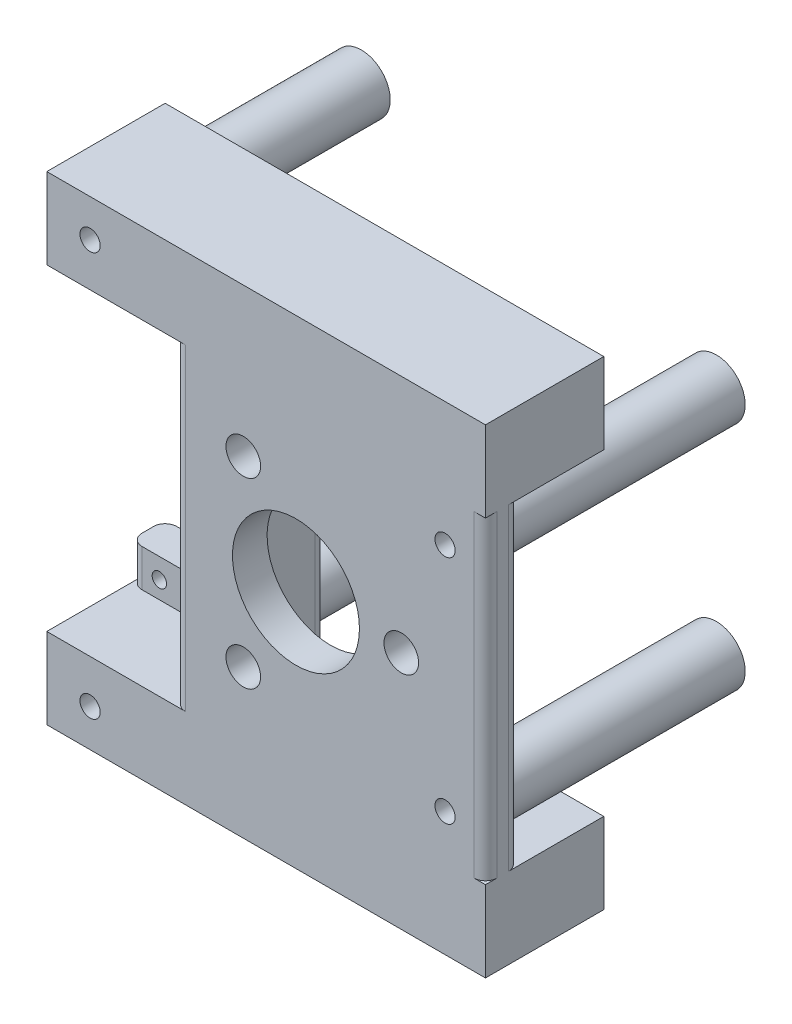
SolidWorks part; units mm, degrees
ref_plane "Front Plane" through (0, 0, 0) normal (0, 0, 1) x (1, 0, 0)
ref_plane "Top Plane" through (0, 0, 0) normal (0, 1, 0) x (1, 0, 0)
ref_plane "Right Plane" through (0, 0, 0) normal (1, 0, 0) x (0, 0, -1)
sketch "Sketch1" plane through (0, 0, 0) normal (0, 0, 1) x (1, 0, 0)
  line L0 (0, 52) -> (28, 52) construction
  line L1 (0, 0) -> (28, 0)
  line L2 (0, 0) -> (0, 55)
  line L3 (0, 55) -> (28, 55)
  line L4 (28, 0) -> (28, 55)
  line L5 (0, 3) -> (28, 3) construction
  circle A0 centre (5, 52) radius 1.25
  circle A1 centre (15, 52) radius 1.25
  circle A2 centre (5, 3) radius 1.25
  circle A3 centre (15, 3) radius 1.25
  dimension "D3" = 2.5
  dimension "D1" = 28
  dimension "D2" = 55
  dimension "D4" = 5
  dimension "D5" = 5
  dimension "D6" = 10
  dimension "D7" = 10
  dimension "D8" = 3
  dimension "D9" = 3
extrude "Boss-Extrude1" add sketch "Sketch1" along normal blind 6
sketch "Sketch2" plane through (0, 0, 6) normal (0, 0, 1) x (1, 0, 0)
  line L0 (0, 0) -> (28, 0) construction
  line L1 (28, 55) -> (22, 55)
  line L2 (28, 55) -> (28, 0)
  line L3 (28, 0) -> (22, 0)
  line L4 (22, 55) -> (22, 0)
  dimension "D1" = 6
extrude "Boss-Extrude2" add sketch "Sketch2" along normal blind 14.5
sketch "Sketch3" plane through (28, 0, 0) normal (1, 0, 0) x (0, 0, -1)
  line L0 (-20.5, 0) -> (0, 0) construction
  line L1 (-20.5, 55) -> (-14.5, 55)
  line L2 (-20.5, 55) -> (-20.5, 0)
  line L3 (-20.5, 0) -> (-14.5, 0)
  line L4 (-14.5, 55) -> (-14.5, 0)
  dimension "D1" = 6
extrude "Boss-Extrude3" add sketch "Sketch3" along normal blind 48
sketch "Sketch4" plane through (0, 0, 20.5) normal (0, 0, 1) x (1, 0, 0)
  line L0 (34.0412, 55) -> (34.0412, 43.305) construction
  line L1 (76, 55) -> (22, 55) construction
  line L2 (22, 55) -> (22, 0) construction
  line L3 (22, 0) -> (76, 0) construction
  line L5 (43.1662, 27.5) -> (32.5412, 45.903) construction
  line L6 (34.0412, 11.695) -> (43.1662, 27.5) construction
  line L7 (43.1662, 27.5) -> (61.4162, 27.5) construction
  line L8 (22, 18) -> (0, 18) construction
  line L9 (0, 55) -> (0, 0) construction
  line L10 (10, 18) -> (43.1662, 27.5) construction
  line L11 (34.0412, 11.695) -> (34.0412, 0) construction
  line L12 (0, 0) -> (22, 0) construction
  circle A0 centre (61.4162, 27.5) radius 3
  circle A1 centre (34.0412, 11.695) radius 3
  circle A2 centre (43.1662, 27.5) radius 21.25 construction
  circle A3 centre (34.0412, 43.305) radius 3
  circle A4 centre (43.1662, 27.5) radius 11
  point P18 (10, 18)
  dimension "D2" = 42.5
  dimension "D3" = 6
  dimension "D4" = 120
  dimension "D8" = 22
  dimension "D1" = 120
  dimension "D5" = 10
  dimension "D6" = 34.5
  dimension "D7" = 18
extrude "Cut-Extrude1" cut sketch "Sketch4" against normal blind 48
fillet "Fillet4" radius 2 7 edges at (22, 27.5, 20.5) (0, 27.5, 6) (0, 27.5, 0) (76, 27.5, 14.5) (28, 27.5, 0) (76, 27.5, 20.5)
sketch "Sketch5" plane through (0, 0, 6) normal (0, 0, 1) x (1, 0, 0)
  line L0 (22, 55) -> (2, 55) construction
  line L1 (0, 48.5) -> (21, 48.5)
  line L2 (0, 48.5) -> (0, 6.5)
  line L3 (0, 6.5) -> (21, 6.5)
  line L4 (21, 48.5) -> (21, 6.5)
  line L5 (2, 0) -> (22, 0) construction
  line L8 (0, 0) -> (0, 55) construction
  dimension "D1" = 6.5
  dimension "D2" = 6.5
  dimension "D3" = 21
extrude "Cut-Extrude2" cut sketch "Sketch5" against normal blind 10
fillet "Fillet5" radius 2 1 edges
sketch "Esquisse2" plane through (0, 0, 14.5) normal (0, 0, -1) x (-1, 0, 0)
  line L0 (-74, 0) -> (-30, 0) construction
  line L3 (-69, 47.5) -> (-69, 7.5)
  circle A0 centre (-69, 47.5) radius 5
  circle A1 centre (-69, 7.5) radius 5
  dimension "D3" = 10
  dimension "D5" = 10
  dimension "D1" = 7.5
  dimension "D4" = 40
extrude "Boss.-Extru.3" add sketch "Esquisse2" along normal blind 41 contours A1 | A0 region at (65.5645, 10.9355, 14.5) region at (72.4355, 50.9355, 14.5)
sketch "Esquisse3" plane through (0, 0, -26.5) normal (0, 0, -1) x (-1, 0, 0)
  circle A0 centre (-69, 7.5) radius 1.75
  circle A1 centre (-69, 47.5) radius 1.75
  dimension "D1" = 3.5
  dimension "D2" = 3.5
extrude "Enlèv. mat.-Extru.1" cut sketch "Esquisse3" against normal through all
sketch "Esquisse4" plane through (0, 55, 0) normal (0, 1, 0) x (1, 0, 0)
  line L1 (0, 0) -> (76, 0)
  line L2 (0, 0) -> (0, -20.5)
  line L3 (0, -20.5) -> (76, -20.5)
  line L4 (76, 0) -> (76, -20.5)
extrude "Boss.-Extru.4" add sketch "Esquisse4" along normal blind 14
sketch "Esquisse5" plane through (0, 0, 0) normal (0, -1, 0) x (1, 0, 0)
  line L0 (76, 16.5) -> (76, 0) construction
  line L1 (0, 20.5) -> (76, 20.5)
  line L2 (0, 20.5) -> (0, 0)
  line L3 (0, 0) -> (76, 0)
  line L4 (76, 20.5) -> (76, 0)
  line L5 (76, 0) -> (26, 0) construction
extrude "Boss.-Extru.5" add sketch "Esquisse5" along normal blind 14
sketch "Esquisse7" plane through (0, 0, 0) normal (0, 0, -1) x (-1, 0, 0)
  line L0 (0, -14) -> (-76, -14) construction
  line L4 (-7.5, -7.5) -> (-7.5, 62.5)
  circle A0 centre (-7.5, -7.5) radius 5
  circle A1 centre (-7.5, 62.5) radius 5
  dimension "D3" = 10
  dimension "D5" = 10
  dimension "D1" = 6.5
  dimension "D4" = 70
extrude "Boss.-Extru.8" add sketch "Esquisse7" along normal blind 26.5 contours A0 | A1 region at (10.9355, 65.9355, 0) region at (4.0645, -4.0645, 0)
sketch "Esquisse10" plane through (0, 0, -26.5) normal (0, 0, -1) x (-1, 0, 0)
  circle A0 centre (-7.5, 62.5) radius 1.75
  circle A1 centre (-7.5, -7.5) radius 1.75
  dimension "D1" = 3.5
  dimension "D2" = 3.5
extrude "Enlèv. mat.-Extru.2" cut sketch "Esquisse10" against normal through all
sketch "Esquisse11" plane through (0, 0, -26.5) normal (0, 0, -1) x (-1, 0, 0)
  line L0 (0, -14) -> (-76, -14) construction
  line L1 (-9.1454, -4.65) -> (-10.7909, -7.5)
  line L2 (-10.7909, -7.5) -> (-9.1454, -10.35)
  line L3 (-9.1454, -10.35) -> (-5.8546, -10.35)
  line L4 (-5.8546, -10.35) -> (-4.2091, -7.5)
  line L5 (-4.2091, -7.5) -> (-5.8546, -4.65)
  line L6 (-5.8546, -4.65) -> (-9.1454, -4.65)
  circle A0 centre (-7.5, -7.5) radius 2.85 construction
  dimension "D1" = 5.7
extrude "Enlèv. mat.-Extru.3" cut sketch "Esquisse11" against normal blind 4.1
sketch "Esquisse12" plane through (0, 0, -26.5) normal (0, 0, -1) x (-1, 0, 0)
  line L0 (-76, 69) -> (0, 69) construction
  line L1 (-9.1454, 65.35) -> (-10.7909, 62.5)
  line L2 (-10.7909, 62.5) -> (-9.1454, 59.65)
  line L3 (-9.1454, 59.65) -> (-5.8546, 59.65)
  line L4 (-5.8546, 59.65) -> (-4.2091, 62.5)
  line L5 (-4.2091, 62.5) -> (-5.8546, 65.35)
  line L6 (-5.8546, 65.35) -> (-9.1454, 65.35)
  line L7 (-74, 55) -> (-30, 55) construction
  line L8 (-70.6454, 50.35) -> (-72.2909, 47.5)
  line L9 (-72.2909, 47.5) -> (-70.6454, 44.65)
  line L10 (-70.6454, 44.65) -> (-67.3546, 44.65)
  line L11 (-67.3546, 44.65) -> (-65.7091, 47.5)
  line L12 (-65.7091, 47.5) -> (-67.3546, 50.35)
  line L13 (-67.3546, 50.35) -> (-70.6454, 50.35)
  line L14 (-26, 0) -> (-76, 0) construction
  line L15 (-70.6454, 10.35) -> (-72.2909, 7.5)
  line L16 (-72.2909, 7.5) -> (-70.6454, 4.65)
  line L17 (-70.6454, 4.65) -> (-67.3546, 4.65)
  line L18 (-67.3546, 4.65) -> (-65.7091, 7.5)
  line L19 (-65.7091, 7.5) -> (-67.3546, 10.35)
  line L20 (-67.3546, 10.35) -> (-70.6454, 10.35)
  circle A0 centre (-7.5, 62.5) radius 2.85 construction
  circle A1 centre (-69, 47.5) radius 2.85 construction
  circle A2 centre (-69, 7.5) radius 2.85 construction
  dimension "D1" = 5.7
  dimension "D2" = 5.7
  dimension "D3" = 5.7
extrude "Enlèv. mat.-Extru.4" cut sketch "Esquisse12" against normal blind 4.1
